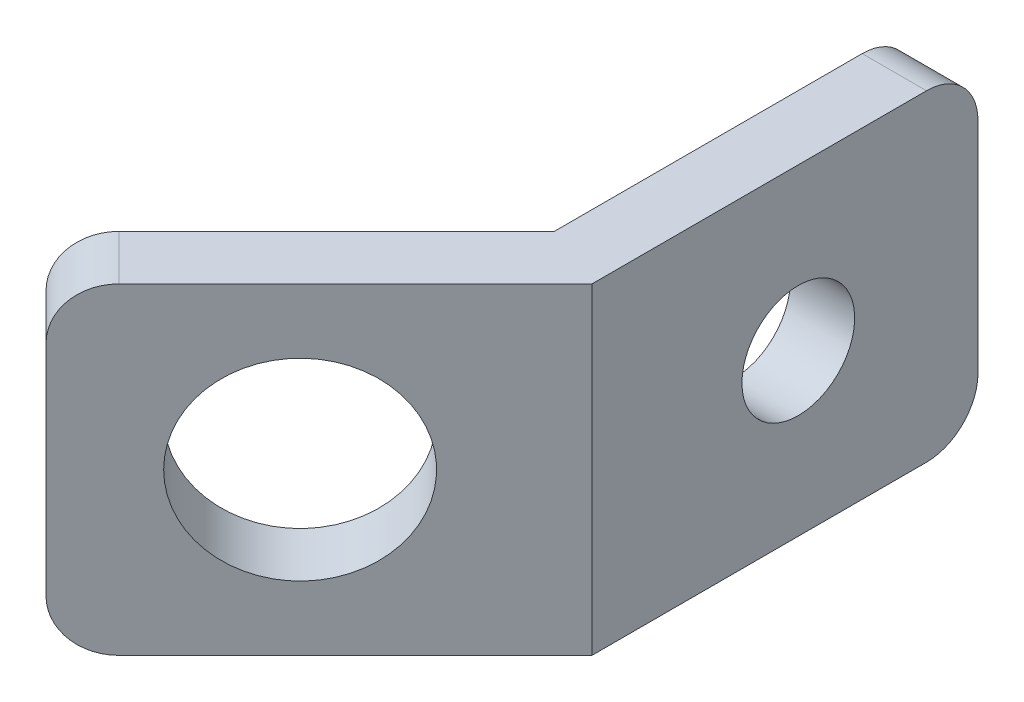
SolidWorks part; units mm, degrees
ref_plane "Front Plane" through (0, 0, 0) normal (0, 0, 1) x (1, 0, 0)
ref_plane "Top Plane" through (0, 0, 0) normal (0, 1, 0) x (1, 0, 0)
ref_plane "Right Plane" through (0, 0, 0) normal (1, 0, 0) x (0, 0, -1)
sketch "Sketch1" plane through (0, 0, 0) normal (0, 1, 0) x (1, 0, 0)
  line L0 (0, 0) -> (0, 19.05)
  line L1 (0, 19.05) -> (-3.175, 19.05)
  line L2 (-3.175, 19.05) -> (-3.175, 1.3151)
  line L3 (-3.175, 1.3151) -> (-15.7154, -11.2253)
  line L4 (-15.7154, -11.2253) -> (-13.4704, -13.4704)
  line L5 (-13.4704, -13.4704) -> (0, 0)
  dimension "D1" = 3.175
  dimension "D2" = 3.175
  dimension "D3" = 19.05
  dimension "D4" = 19.05
  dimension "D5" = 135
extrude "Boss-Extrude1" add sketch "Sketch1" along normal blind 15.875
sketch "Sketch3" plane through (-3.175, 0, 0) normal (-1, 0, 0) x (0, 0, 1)
  line L0 (-10.1826, 15.875) -> (-10.1826, 0) construction
  line L1 (-19.05, 15.875) -> (-1.3151, 15.875) construction
  line L2 (-19.05, 0) -> (-1.3151, 0) construction
  circle A0 centre (-10.1826, 7.9375) radius 2.7813
  dimension "D1" = 5.5626
extrude "Cut-Extrude1" cut sketch "Sketch3" against normal through all
sketch "Sketch4" plane through (-2.2451, 0, -2.2451) normal (-0.7071, 0, -0.7071) x (-0.7071, 0, 0.7071)
  line L0 (10.1826, 0) -> (10.1826, 15.875) construction
  line L1 (1.3151, 0) -> (19.05, 0) construction
  line L2 (1.3151, 15.875) -> (19.05, 15.875) construction
  circle A0 centre (10.1826, 7.9375) radius 4.7625
  dimension "D1" = 9.525
extrude "Cut-Extrude2" cut sketch "Sketch4" against normal through all
fillet "Fillet1" radius 2.54 4 edges at (-1.5875, 15.875, -19.05) (-1.5875, 0, -19.05) (-14.5929, 0, 12.3479) (-14.5929, 15.875, 12.3479)
